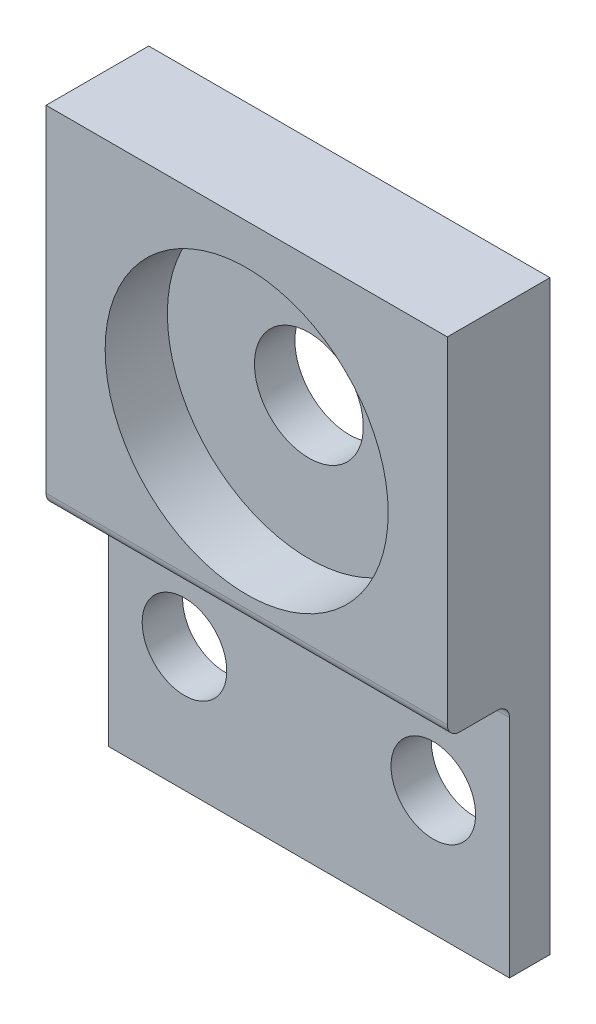
SolidWorks part; units mm, degrees
material "ABS"
ref_plane "Front Plane" through (0, 0, 0) normal (0, 0, 1) x (1, 0, 0)
ref_plane "Top Plane" through (0, 0, 0) normal (0, 1, 0) x (1, 0, 0)
ref_plane "Right Plane" through (0, 0, 0) normal (1, 0, 0) x (0, 0, -1)
sketch "Sketch1" plane through (0, 0, 0) normal (0, 0, 1) x (1, 0, 0)
  line L0 (16.125, 10) -> (16.125, 0) construction
  line L3 (6.125, 10) -> (26.125, 10) construction
  line L5 (0, 0) -> (32.25, 0)
  line L6 (0, 0) -> (0, 19.125)
  line L7 (0, 19.125) -> (32.25, 19.125)
  line L8 (32.25, 0) -> (32.25, 19.125)
  line L13 (0, 32.5) -> (32.25, 32.5) construction
  line L14 (16.125, 43.875) -> (16.125, 47.125) construction
  line L15 (0, 19.125) -> (0, 47.125)
  line L16 (0, 47.125) -> (32.25, 47.125)
  line L17 (32.25, 19.125) -> (32.25, 47.125)
  circle A0 centre (6.125, 10) radius 3.4004
  circle A1 centre (26.125, 10) radius 3.4004
  circle A4 centre (16.125, 32.5) radius 11.375
  circle A5 centre (16.125, 32.5) radius 4.375
  point P0 (16.125, 21.125)
  dimension "D2" = 20
  dimension "D4" = 22.75
  dimension "D7" = 8.75
  dimension "D1" = 10
  dimension "D3" = 32.25
  dimension "D5" = 3.25
  dimension "D6" = 22.5
  dimension "D8" = 2
extrude "Boss-Extrude1" add sketch "Sketch1" along normal blind 3.25 contours L5 L8 L7 L6 A1 A0 | L7 L17 L16 L15 A4 | A4 A5 region at (16.125, 9.5041, 0) region at (0.4271, 33.125, 0) region at (5.0717, 32.5, 0)
extrude "Boss-Extrude2" add sketch "Sketch1<3>" along normal blind 8.25 contours L7 L17 L16 L15 A4 region at (0.4271, 33.125, 0)
sketch "Sketch1<3>" plane through (0, 0, 0) normal (0, 0, 1) x (1, 0, 0) same geometry as "Sketch1"
fillet "Fillet1" radius 1 2 edges at (16.125, 19.125, 8.25) (16.125, 19.125, 3.25)
